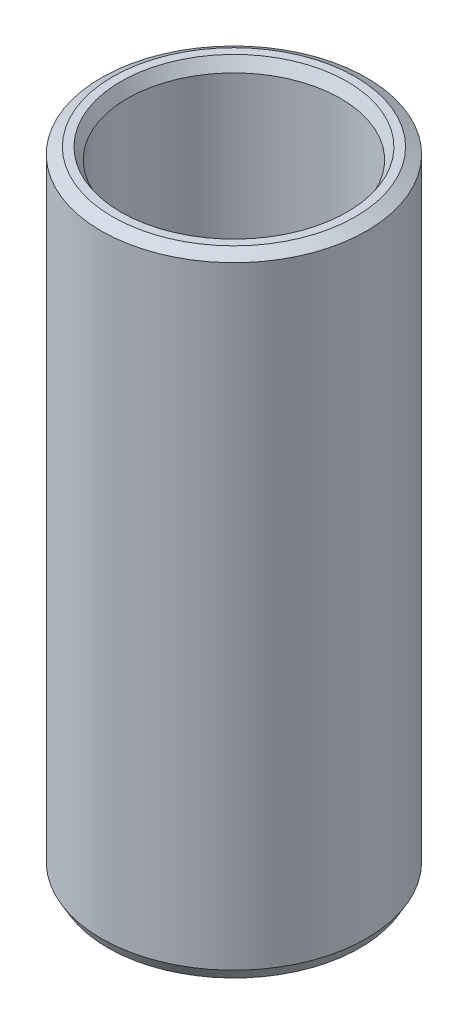
SolidWorks part; units mm, degrees
ref_plane "Front Plane" through (0, 0, 0) normal (0, 0, 1) x (1, 0, 0)
ref_plane "Top Plane" through (0, 0, 0) normal (0, 1, 0) x (1, 0, 0)
ref_plane "Right Plane" through (0, 0, 0) normal (1, 0, 0) x (0, 0, -1)
sketch "Sketch1" plane through (0, 0, 0) normal (0, 1, 0) x (1, 0, 0)
  circle A0 centre (0, 0) radius 55
  dimension "SLEEVE_OD" = 110
extrude "Boss-Extrude1" add sketch "Sketch1" along normal blind 261.3636
sketch "Sketch2" plane through (0, 0, 0) normal (0, 1, 0) x (1, 0, 0)
  circle A0 centre (0, 0) radius 44.17
  dimension "BORE_D" = 88.34
extrude "Cut-Extrude1" cut sketch "Sketch2" along normal through all
chamfer "Chamfer1" distance 2.7206 angle 60 4 edges at (0, 261.3636, 44.17) (0, 0, 44.17) (0, 0, 55) (0, 261.3636, 55) first distance on face at (0, 261.3636, 44.17) first distance on face at (0, 0, 44.17) first distance on face at (0, 261.3636, 55)
